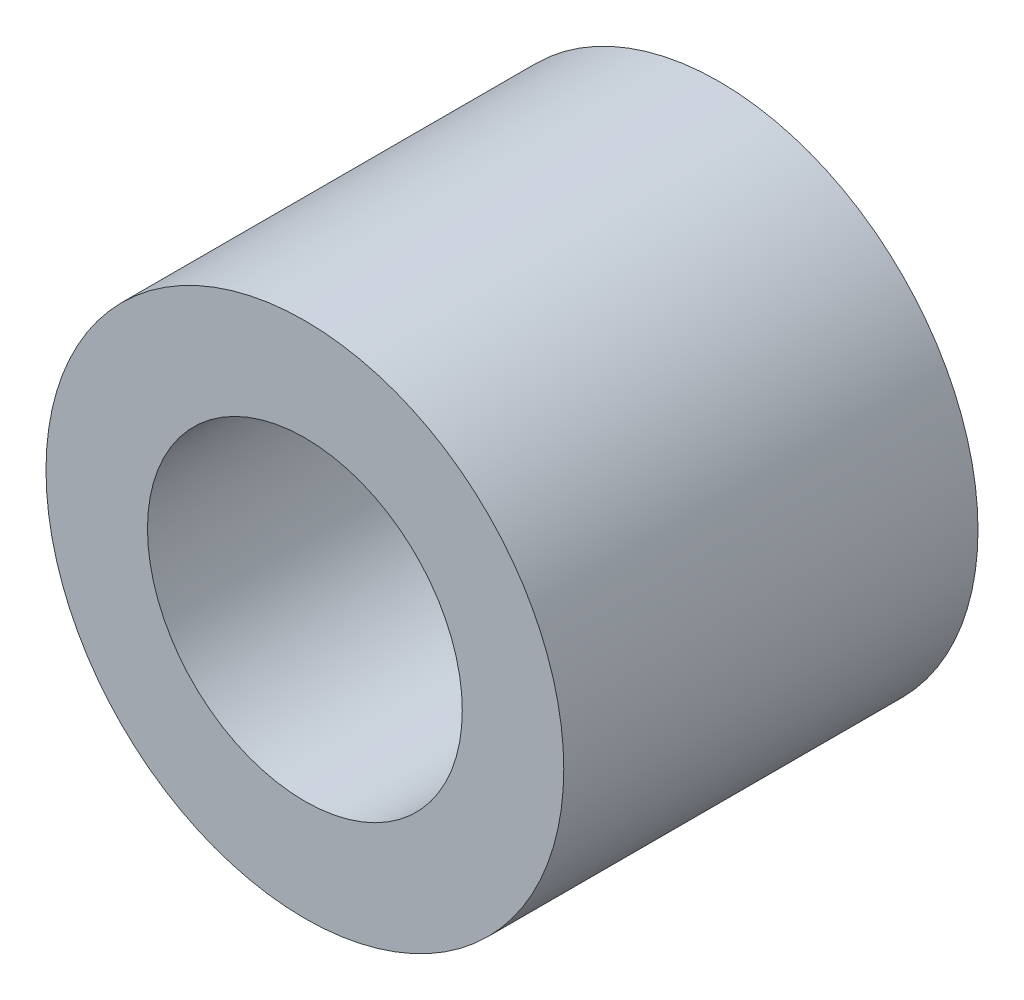
SolidWorks part; units mm, degrees
ref_plane "Front Plane" through (0, 0, 0) normal (0, 0, 1) x (1, 0, 0)
ref_plane "Top Plane" through (0, 0, 0) normal (0, 1, 0) x (1, 0, 0)
ref_plane "Right Plane" through (0, 0, 0) normal (1, 0, 0) x (0, 0, -1)
sketch "Sketch1" plane through (0, 0, 0) normal (0, 0, 1) x (1, 0, 0)
  circle A0 centre (0, 0) radius 7.9375 construction
  circle A1 centre (0, 0) radius 4.826 construction
  point P4 (0, 7.9375)
  dimension "ID" = 9.652
  dimension "OD" = 15.875
sketch "Sketch2" plane through (0, 0, 0) normal (1, 0, 0) x (0, 0, -1)
  line L0 (-152.4, 7.9375) -> (152.4, 7.9375) construction
  point P2 (132.5563, 7.9375)
  point P3 (-132.5563, 7.9375)
  dimension "Length" = 304.8
  dimension "D1" = 19.8438
  dimension "D2" = 19.8438
sketch "Sketch3" plane through (0, 0, 0) normal (0, 0, 1) x (1, 0, 0)
  circle A0 centre (0, 0) radius 4.826 construction
  circle A1 centre (0, 0) radius 7.9375 construction
  circle A2 centre (0, 0) radius 4.826
  circle A3 centre (0, 0) radius 7.9375
extrude "Boss-Extrude1" add sketch "Sketch3" against normal up to vertex (152.4 mm away) and the other way up to vertex (152.4 mm away) up to point (0, 7.9375, -152.4) other way up to point (0, 7.9375, 152.4)
sketch "Sketch4" plane through (0, 0, 152.4) normal (0, 0, 1) x (1, 0, 0)
  circle A0 centre (0, 0) radius 7.9375
extrude "Cut-Extrude1" cut sketch "Sketch4" against normal blind 292.1
equation "\"D1@Sketch2\"=\"OD@Sketch1\"*1.25"
equation "\"D2@Sketch2\"=\"D1@Sketch2\""
